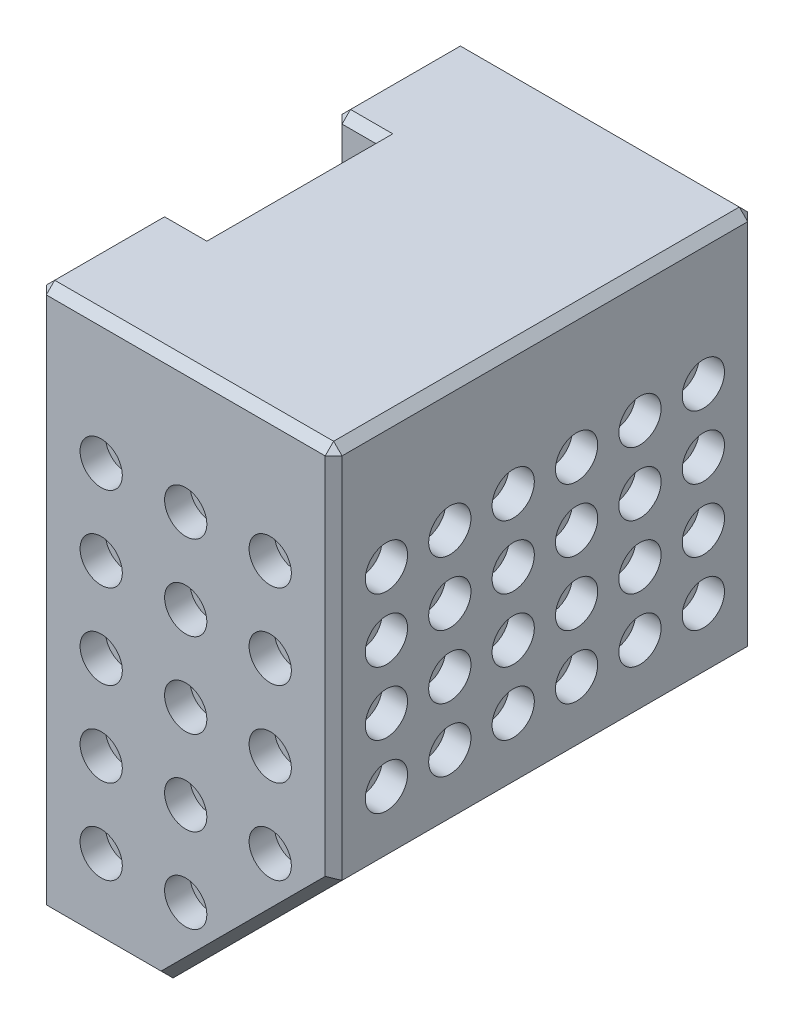
SolidWorks part; units mm, degrees
material "K110"
ref_plane "Front Plane" through (0, 0, 0) normal (0, 0, 1) x (1, 0, 0)
ref_plane "Top Plane" through (0, 0, 0) normal (0, 1, 0) x (1, 0, 0)
ref_plane "Right Plane" through (0, 0, 0) normal (1, 0, 0) x (0, 0, -1)
sketch "Sketch1" plane through (0, 0, 0) normal (0, 1, 0) x (1, 0, 0)
  line L1 (-17.5, -25) -> (17.5, -25)
  line L2 (-17.5, -25) -> (-17.5, 25)
  line L3 (-17.5, 25) -> (17.5, 25)
  line L4 (17.5, -25) -> (17.5, 25)
  line L5 (-17.5, -25) -> (17.5, 25) construction
  line L6 (-17.5, 25) -> (17.5, -25) construction
  point P0 (0, 0)
  dimension "D1" = 50
  dimension "D2" = 35
extrude "Boss-Extrude1" add sketch "Sketch1" against normal blind 64.5
sketch "Sketch2" plane through (0, 0, 25) normal (0, 0, 1) x (1, 0, 0)
  line L0 (-2.5, -64.5) -> (17.5, -44.5)
  line L1 (-17.5, -64.5) -> (17.5, -64.5) construction
  line L2 (17.5, -64.5) -> (17.5, 0) construction
  line L3 (17.5, -44.5) -> (17.5, -64.5)
  line L4 (17.5, -64.5) -> (-2.5, -64.5)
  dimension "D1" = 20
  dimension "D2" = 45
extrude "Cut-Extrude1" cut sketch "Sketch2" against normal up to next
sketch "Sketch3" plane through (-17.5, 0, 0) normal (-1, 0, 0) x (0, 0, 1)
  line L0 (-25, -64.5) -> (25, -64.5) construction
  line L1 (-7, -64.5) -> (7, -64.5)
  line L2 (-7, -64.5) -> (-7, -44.5)
  line L3 (-7, -44.5) -> (7, -44.5)
  line L4 (7, -64.5) -> (7, -44.5)
  line L5 (-25, -44.5) -> (25, -44.5) construction
  point P8 (0, -44.5)
  dimension "D1" = 14
  dimension "D2" = 20
extrude "Cut-Extrude2" cut sketch "Sketch3" against normal up to next
fillet "Fillet1" 2 edges at (0, -44.5, -7) (0, -44.5, 7) type full round first side face at (-5, -54.5, -7) second side face at (-5, -54.5, 7) middle face at (0, -44.5, 0)
sketch "Sketch4" plane through (0, 0, 0) normal (0, 1, 0) x (1, 0, 0)
  line L0 (-17.5, 0) -> (17.5, 0) construction
  line L1 (-17.5, 25) -> (-17.5, -25) construction
  line L2 (17.5, -25) -> (17.5, 25) construction
  line L4 (-17.5, -10) -> (-12.5, -10)
  line L5 (-17.5, -10) -> (-17.5, 10)
  line L6 (-17.5, 10) -> (-12.5, 10)
  line L7 (-12.5, -10) -> (-12.5, 10)
  dimension "D1" = 5
  dimension "D2" = 20
extrude "Cut-Extrude3" cut sketch "Sketch4" against normal blind 43
sketch "Sketch5" plane through (-17.5, 0, 0) normal (-1, 0, 0) x (0, 0, 1)
  line L0 (-10, -43) -> (-10, 0) construction
  line L1 (-15, -43) -> (15, -43)
  line L2 (-15, -43) -> (-15, -38)
  line L3 (-15, -38) -> (15, -38)
  line L4 (15, -43) -> (15, -38)
  line L5 (-10, -43) -> (10, -43) construction
  line L6 (10, -43) -> (10, 0) construction
  dimension "D1" = 5
  dimension "D2" = 5
  dimension "D3" = 5
extrude "Cut-Extrude4" cut sketch "Sketch5" against normal up to surface (5 mm away) up to face at (-12.5, -21.5, 0)
fillet "Fillet5" 2 edges at (-15, -43, -15) (-15, -38, -15) type full round first side face at (-15, -43, 0) second side face at (-15, -38, -12.5) middle face at (-15, -40.5, -15)
fillet "Fillet6" 2 edges at (-15, -43, 15) (-15, -38, 15) type full round first side face at (-15, -43, 1.25) second side face at (-15, -38, 12.5) middle face at (-15, -40.5, 15)
chamfer "Chamfer1" distance 1 angle 45 28 edges at (-17.5, -38, 11.25) (-17.5, -19, 10) (-17.5, -64.5, 16) (-17.5, -58, 7) (-17.5, -44.5, 0) (-17.5, -58, -7) (-17.5, -64.5, -16) (-17.5, -40.5, 15) (-17.5, -43, 0) (-17.5, -40.5, -15) (-17.5, -38, -11.25) (-17.5, -19, -10) (17.5, 0, 0) (17.5, -22.25, -25) (0, 0, -25) (7.5, -54.5, -25) (-10, -64.5, -25) (-17.5, -32.25, -25) (-17.5, 0, -17.5) (-15, 0, -10) (-12.5, 0, 0) (-15, 0, 10) (-17.5, 0, 17.5) (-10, -64.5, 25) (-17.5, -32.25, 25) (0, 0, 25) (17.5, -22.25, 25) (7.5, -54.5, 25)
sketch "Sketch6" plane through (0, 0, 25) normal (0, 0, 1) x (1, 0, 0)
  line L0 (-16.5, 0) -> (16.5, 0) construction
  line L1 (-17.5, -63.5) -> (-17.5, -1) construction
  circle A0 centre (-10, -15) radius 2.5
  dimension "D1" = 5
  dimension "D2" = 15
  dimension "D3" = 7.5
extrude "Cut-Extrude5" cut sketch "Sketch6" against normal blind 3
pattern_linear "LPattern1" count 3 spacing 10 along (1, 0, 0) count 5 spacing 10 along (0, -1, 0) skipping (2, 4) of "Cut-Extrude5"
sketch "Sketch9" plane through (17.5, 0, 0) normal (1, 0, 0) x (0, 0, -1)
  line L0 (-25, -44.0858) -> (-25, -1) construction
  line L1 (-24, 0) -> (24, 0) construction
  circle A0 centre (-18.75, -15) radius 2.5
  dimension "D1" = 5
  dimension "D2" = 6.25
  dimension "D3" = 15
extrude "Cut-Extrude20" cut sketch "Sketch9" against normal blind 3
pattern_linear "LPattern2" count 4 spacing 7.5 along (0, -1, 0) count 6 spacing 7.5 along (0, 0, -1) of "Cut-Extrude20"
sketch "Sketch10" plane through (-17.5, 0, 0) normal (-1, 0, 0) x (0, 0, 1)
  line L0 (-11, -1) -> (-24, -1) construction
  line L2 (-24, 0) -> (-11, 0) construction
  circle A0 centre (-17.5, -15) radius 2.5
  point P7 (-17.5, -1)
  dimension "D1" = 5
  dimension "D2" = 15
extrude "Cut-Extrude21" cut sketch "Sketch10" against normal blind 3
pattern_linear "LPattern3" count 7 spacing 7.5 along (0, -1, 0) count 2 spacing 35 along (0, 0, 1) of "Cut-Extrude21"
sketch "Sketch11" plane through (31, -31, 0) normal (0.7071, -0.7071, 0) x (0, 0, -1)
  line L0 (-25, -46.9619) -> (-25, -19.5061) construction
  line L2 (0, -19.0919) -> (-24, -19.0919) construction
  circle A0 centre (-18.75, -26.5919) radius 2.5
  dimension "D1" = 6.25
  dimension "D2" = 5
  dimension "D5" = 7.5
extrude "Cut-Extrude23" cut sketch "Sketch11" against normal blind 3
pattern_linear "LPattern5" count 6 spacing 7.5 along (0, 0, -1) count 3 spacing 7.5 along (-0.7071, -0.7071, 0) skipping (2, 0), (2, 1), (2, 2), (3, 0), (3, 1), (3, 2) of "Cut-Extrude23"
sketch "Sketch18" plane through (0, 0, -25) normal (0, 0, -1) x (-1, 0, 0)
  circle A0 centre (10, -15) radius 2.5
extrude "Cut-Extrude25" cut sketch "Sketch18" against normal blind 3
pattern_linear "LPattern7" count 3 spacing 10 along (1, 0, 0) count 5 spacing 10 along (0, -1, 0) of "Cut-Extrude25"
